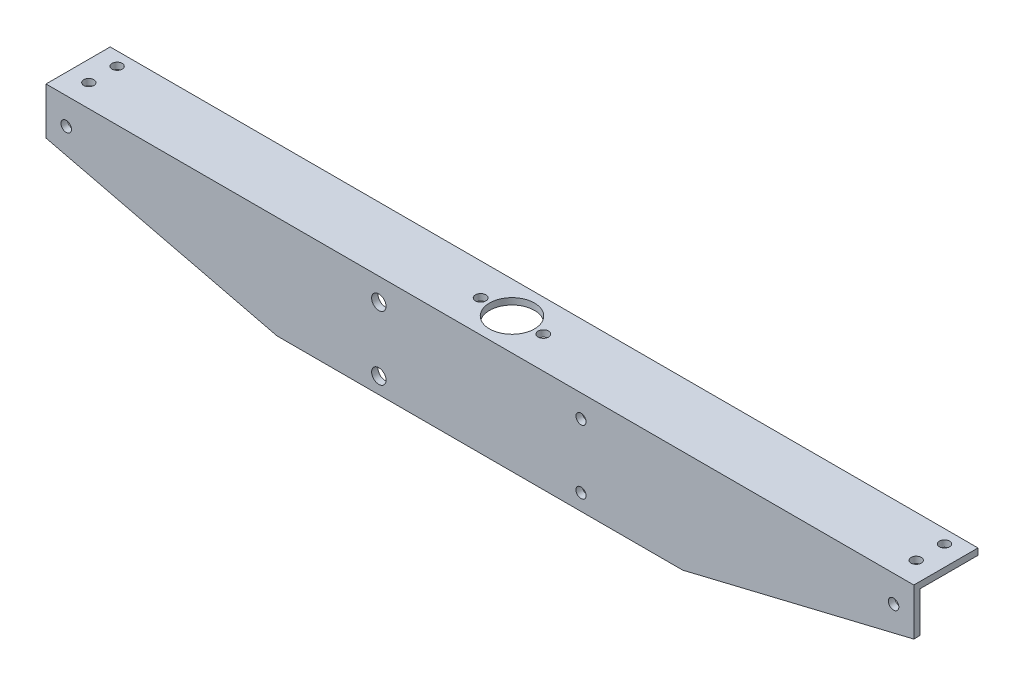
SolidWorks part; units mm, degrees
material "6063-T5"
ref_plane "Front Plane" through (0, 0, 0) normal (0, 0, 1) x (1, 0, 0)
ref_plane "Top Plane" through (0, 0, 0) normal (0, 1, 0) x (1, 0, 0)
ref_plane "Right Plane" through (0, 0, 0) normal (1, 0, 0) x (0, 0, -1)
sketch "Sketch1" plane through (0, 0, 0) normal (1, 0, 0) x (0, 0, -1)
  line L0 (0, 0) -> (31.75, 0)
  line L1 (31.75, 0) -> (31.75, -3.175)
  line L2 (31.75, -3.175) -> (3.175, -3.175)
  line L3 (3.175, -3.175) -> (3.175, -50.8)
  line L4 (3.175, -50.8) -> (0, -50.8)
  line L5 (0, -50.8) -> (0, 0)
  dimension "D1" = 31.75
  dimension "D2" = 3.175
  dimension "D3" = 3.175
  dimension "D4" = 50.8
extrude "Boss-Extrude1" add sketch "Sketch1" along normal mid plane 429.26
sketch "Sketch2" plane through (0, 0, -3.175) normal (0, 0, -1) x (-1, 0, 0)
  line L0 (0, 0) -> (0, -57.8721) construction
  line L1 (-214.63, -50.8) -> (214.63, -50.8) construction
  line L3 (-214.63, -3.175) -> (214.63, -3.175) construction
  circle A0 centre (-50, -11.175) radius 2.5
  circle A1 centre (50, -11.175) radius 3.57
  circle A2 centre (50, -42.8) radius 3.57
  circle A3 centre (-50, -42.8) radius 2.5
  dimension "D1" = 5
  dimension "D2" = 5
  dimension "D3" = 7.14
  dimension "D4" = 7.14
  dimension "D7" = 8
  dimension "D9" = 8
  dimension "D5" = 50
  dimension "D6" = 50
extrude "Cut-Extrude1" cut sketch "Sketch2" against normal through all
sketch "Sketch3" plane through (0, 0, -3.175) normal (0, 0, -1) x (-1, 0, 0)
  line L0 (214.63, -50.8) -> (100.33, -50.8)
  line L1 (-214.63, -50.8) -> (214.63, -50.8) construction
  line L2 (100.33, -50.8) -> (214.63, -23.175)
  line L3 (214.63, -50.8) -> (214.63, -3.175) construction
  line L4 (214.63, -23.175) -> (214.63, -50.8)
  line L5 (-214.63, -23.175) -> (-214.63, -50.8)
  line L6 (0, 0) -> (0, -50.8) construction
  line L7 (-100.33, -50.8) -> (-214.63, -23.175)
  line L8 (-214.63, -50.8) -> (-100.33, -50.8)
  dimension "D1" = 20
  dimension "D2" = 114.3
extrude "Cut-Extrude2" cut sketch "Sketch3" against normal blind 3.175
sketch "Sketch4" plane through (0, 0, 0) normal (0, 1, 0) x (1, 0, 0)
  line L0 (0, 0) -> (0, 31.75) construction
  line L1 (214.63, 31.75) -> (-214.63, 31.75) construction
  line L2 (-214.63, 31.75) -> (-214.63, 0) construction
  line L4 (214.63, 0) -> (-214.63, 0) construction
  circle A0 centre (-204.63, 11.176) radius 2.5
  circle A1 centre (-204.63, 25.176) radius 2.5
  circle A2 centre (204.63, 25.176) radius 2.5
  circle A3 centre (204.63, 11.176) radius 2.5
  dimension "D1" = 5
  dimension "D2" = 5
  dimension "D3" = 10
  dimension "D4" = 11.176
  dimension "D5" = 14
extrude "Cut-Extrude3" cut sketch "Sketch4" against normal blind 3.175
sketch "Sketch5" plane through (0, -3.175, 0) normal (0, -1, 0) x (1, 0, 0)
  line L0 (214.63, 0) -> (-214.63, 0) construction
  circle A0 centre (0, -15.875) radius 19.05 construction
  circle A1 centre (0, -15.875) radius 11.1125
  dimension "D1" = 22.225
  dimension "D2" = 38.1
  dimension "D3" = 15.875
extrude "Cut-Extrude4" cut sketch "Sketch5" against normal up to next
sketch "Sketch6" plane through (0, 0, 0) normal (0, 0, 1) x (1, 0, 0)
  line L0 (214.63, 0) -> (214.63, -23.175) construction
  line L1 (214.63, 0) -> (-214.63, 0) construction
  line L2 (0, 0) -> (0, -50.8) construction
  line L3 (100.33, -50.8) -> (-100.33, -50.8) construction
  circle A0 centre (204.63, -13.175) radius 2.6
  circle A1 centre (-204.63, -13.175) radius 2.6
  dimension "D1" = 5.2
  dimension "D3" = 13.175
  dimension "D2" = 10
extrude "Cut-Extrude5" cut sketch "Sketch6" against normal up to surface (3.175 mm away) up to face at (50, -40.3, -3.175)
sketch "Sketch7" plane through (0, 0, 0) normal (0, 1, 0) x (1, 0, 0)
  circle A0 centre (15.5, 15.875) radius 2.6
  circle A1 centre (-15.5, 15.875) radius 2.6
  dimension "D1" = 5.2
extrude "Cut-Extrude6" cut sketch "Sketch7" against normal up to surface (3.175 mm away) up to face at (0, -3.175, -26.9875)
equation "\"D2@Sketch2\"=\"D1@Sketch2\""
equation "\"D4@Sketch2\"=\"D3@Sketch2\""
equation "\"D2@Sketch4\" = \"D1@Sketch4\""
